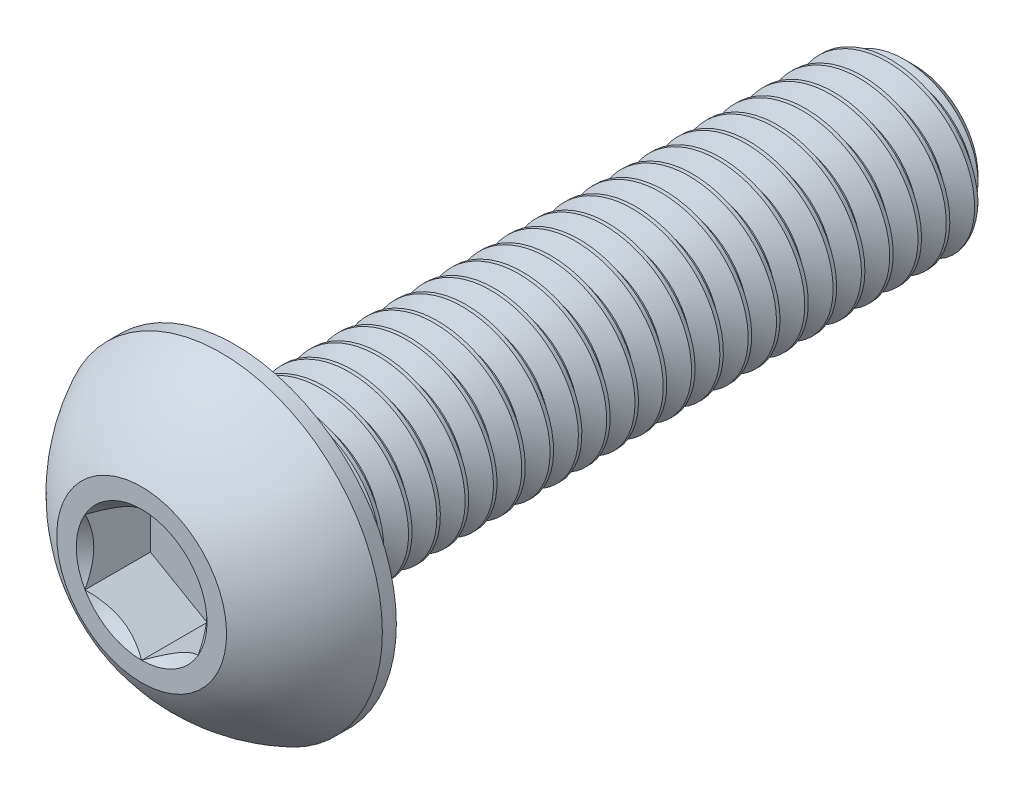
SolidWorks part; units mm, degrees
ref_plane "Front" through (0, 0, 0) normal (0, 0, 1) x (1, 0, 0)
ref_plane "Top" through (0, 0, 0) normal (0, 1, 0) x (1, 0, 0)
ref_plane "Right" through (0, 0, 0) normal (1, 0, 0) x (0, 0, -1)
sketch "Sketch1" plane through (0, 0, 0) normal (1, 0, 0) x (0, 0, -1)
  line L2 (1.65, 1.5) -> (13.65, 1.5)
  line L3 (13.65, 1.5) -> (13.65, 0)
  line L4 (13.65, 0) -> (1.65, 0)
  line L6 (1.4025, 2.85) -> (1.65, 2.85) construction
  line L7 (13.65, 1.5) -> (13.65, -1.5) construction
  line L8 (0, 0) -> (1.65, 0) construction
  line L9 (1.65, 2.85) -> (1.65, -2.85) construction
  line L11 (1.65, 1.5) -> (1.65, 0)
  line L13 (0, 1) -> (0, -1) construction
  line L14 (0, 1) -> (0, 1.5) construction
  line L15 (13.65, -1.5) -> (13.15, -1.5) construction
  arc A3 (0, 1.5) -> (1.4025, 2.85) centre (2.7948, 0) cw construction
  dimension "D1" = 0.2475
  dimension "Pitch" = 0.5
revolve "Revolve1" add sketch "Sketch1" angle 360 mid plane about L4
sketch "Sketch7" plane through (0, 0, 0) normal (1, 0, 0) x (0, 0, -1)
  line L6 (1.4025, 2.85) -> (1.65, 2.85) construction
  line L8 (0, 0) -> (1.65, 0) construction
  line L11 (1.65, 2.85) -> (1.65, -2.85) construction
  line L12 (1.4025, 2.85) -> (1.65, 2.85)
  line L13 (0, 0) -> (1.65, 0)
  line L14 (0, 1) -> (0, -1) construction
  line L15 (1.65, 2.85) -> (1.65, 0)
  line L16 (0, 1.5) -> (0, 0)
  arc A2 (1.4025, 2.85) -> (0, 1.5) centre (2.7948, 0) ccw construction
  arc A3 (1.4025, 2.85) -> (0, 1.5) centre (2.7948, 0) ccw
revolve "Revolve2" add sketch "Sketch7" angle 360 mid plane about L13
sketch "Sketch5" plane through (0, 0, 0) normal (0, 0, 1) x (1, 0, 0)
  line L1 (1, -0.5774) -> (1, 0.5774)
  line L2 (1, 0.5774) -> (0, 1.1547)
  line L3 (0, 1.1547) -> (-1, 0.5774)
  line L4 (-1, 0.5774) -> (-1, -0.5774)
  line L5 (-1, -0.5774) -> (0, -1.1547)
  line L6 (0, -1.1547) -> (1, -0.5774)
  circle A0 centre (0, 0) radius 1 construction
extrude "Cut-Extrude2" cut sketch "Sketch5" against normal blind 1.155
sketch "Sketch6" plane through (0, 0, 0) normal (0, 0, 1) x (1, 0, 0)
  circle A0 centre (0, 0) radius 1.1547
extrude "Cut-Extrude3" cut sketch "Sketch6" against normal blind 1.155 draft 45
sketch "Sketch11" plane through (0, 0, 0) normal (1, 0, 0) x (0, 0, -1)
  line L0 (1.65, -2.85) -> (1.65, 2.85)
  point P4 (1.65, 0)
split "Split1" trim tools "Sketch11" bodies to split 113 resulting bodies 119 120
sketch "Sketch10" plane through (0, 0, 0) normal (1, 0, 0) x (0, 0, -1)
  line L0 (13.65, 1.5) -> (13.65, -1.5) construction
  point P0 (12.9, -1.5)
  dimension "D1" = 0.75
sketch "Sketch3" plane through (0, 0, -13.65) normal (0, 0, -1) x (-1, 0, 0)
  circle A0 centre (0, 0) radius 1.5
curve "Helix/Spiral1" pitch 0.5 height 12.5 radius 1.5 centre (0, 0, -13.65) axis (0, 0, 1) start towards (0, 1, 0)
sketch "Sketch2" plane through (0, 0, 0) normal (1, 0, 0) x (0, 0, -1)
  line L0 (13.6187, 1.5541) -> (14.1187, 1.5541) construction
  line L1 (14.1187, 1.5541) -> (13.8687, 1.1211) construction
  line L2 (13.8687, 1.1211) -> (13.6187, 1.5541) construction
  line L3 (13.8687, 1.5541) -> (13.8687, 1.5) construction
  line L4 (13.8687, 1.5) -> (13.8687, 1.1752) construction
  line L5 (13.8687, 1.1752) -> (13.8687, 1.1211) construction
  line L6 (13.8375, 1.1752) -> (13.9, 1.1752)
  line L7 (13.65, 1.5) -> (14.0875, 1.5) construction
  line L8 (13.6344, 1.5271) -> (14.1031, 1.5271)
  line L9 (13.6344, 1.5271) -> (13.8375, 1.1752)
  line L10 (14.1031, 1.5271) -> (13.9, 1.1752)
  point P10 (13.8687, 1.1752)
  point P13 (13.8687, 1.5)
  point P16 (13.8687, 1.5271)
  dimension "D1" = 0.5
  dimension "D2" = 0.0625
chamfer "Chamfer1" distance 0.375 angle 45 1 edges at (0, 1.5, -13.65)
sweep "Cut-Sweep1" cut profiles "Sketch2" path "Helix/Spiral1" align with end faces yes
combine bodies "Combine1" operation type add bodies to combine 120 114
equation "\"D3@Helix/Spiral1\" = \"Lg@Sketch1\" + \"D4@Helix/Spiral1\""
equation "\"D1@Chamfer1\" = \"D4@Helix/Spiral1\" * .75"
equation "\"D1@Cut-Extrude2\" = \"Head Ht@Sketch1\" * .7"
equation "\"D1@Sketch1\" = \"Head Ht@Sketch1\" * .15"
equation "\"D1@Sketch10\" = \"D4@Helix/Spiral1\" * 1.5"
equation "\"D1@Cut-Extrude3\" = \"D1@Cut-Extrude2\""
equation "\"D4@Helix/Spiral1\"=\"Pitch@Sketch1\""
equation "\"D1@Sketch2\"=\"Pitch@Sketch1\""
equation "\"D2@Sketch2\"=\"D1@Sketch2\"/8"
